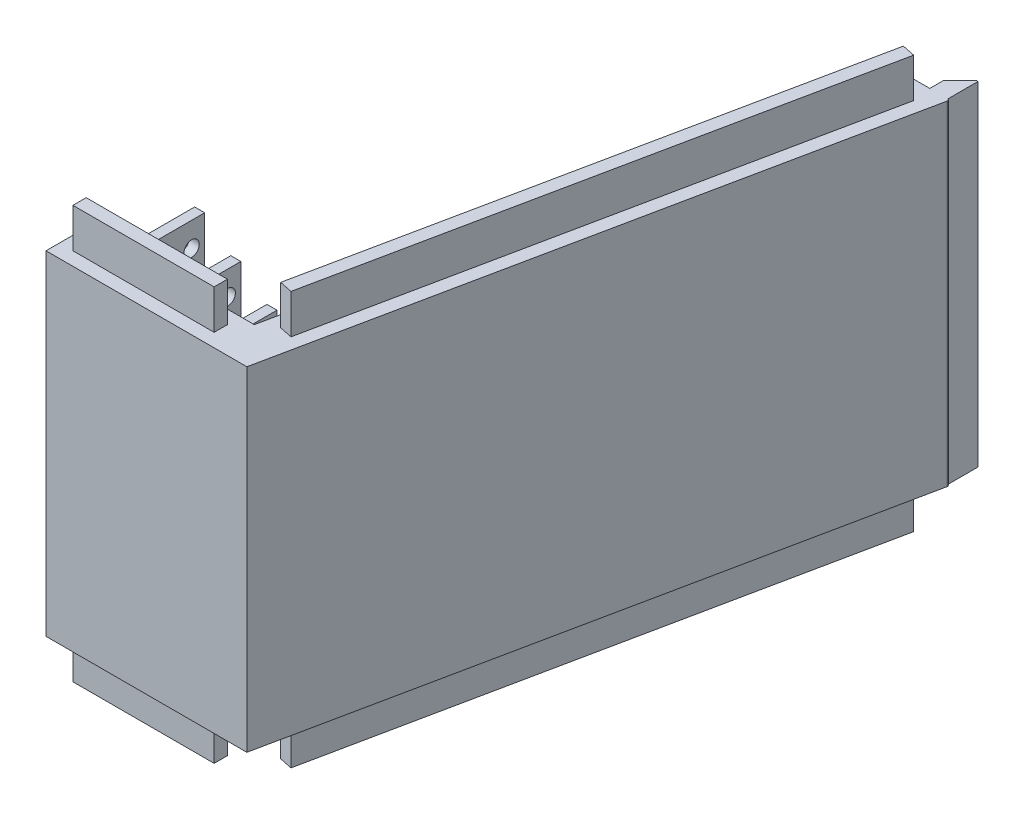
SolidWorks part; units mm, degrees
ref_plane "Front Plane" through (0, 0, 0) normal (1, 0, 0) x (0, 1, 0)
ref_plane "Top Plane" through (0, 0, 0) normal (0, 0, 1) x (0, 1, 0)
ref_plane "Right Plane" through (0, 0, 0) normal (0, 1, 0) x (-1, 0, 0)
sketch "Sketch1" plane through (0, 0, 0) normal (0, 1, 0) x (-1, 0, 0)
  line L0 (-10.3119, 2.5706) -> (19.6881, 147.5706)
  line L1 (-10.3119, -4.9294) -> (-5.3119, -4.9294)
  line L2 (-10.3119, -4.9294) -> (-10.3119, 2.5706)
  line L3 (-10.3119, 2.5706) -> (-5.3119, 2.5706)
  line L4 (-5.3119, -4.9294) -> (-5.3119, 2.5706)
  line L13 (-10.3119, 2.5706) -> (19.6881, 147.5706)
  line L14 (-10.3119, 2.5706) -> (-0.5193, 0.5446)
  line L15 (-10.3119, 2.5706) -> (69.6881, 2.5706) construction
  line L16 (-10.3119, 2.5706) -> (-10.3119, 137.5706) construction
  line L17 (-10.3119, 137.5706) -> (69.6881, 137.5706) construction
  line L18 (69.6881, 2.5706) -> (69.6881, 137.5706) construction
  line L19 (69.6881, 137.5706) -> (19.6881, 137.5706)
  line L20 (69.6881, 137.5706) -> (69.6881, 147.5706)
  line L21 (69.6881, 147.5706) -> (19.6881, 147.5706)
  line L22 (19.6881, 137.5706) -> (19.6881, 147.5706)
  line L23 (19.6881, 147.5706) -> (29.4807, 145.5446)
  line L24 (-0.5193, 0.5446) -> (29.4807, 145.5446)
  line L25 (-5.3119, 2.5706) -> (-0.1001, 2.5706)
  line L27 (-10.3119, 2.5706) -> (-9.8119, 2.5706)
  line L28 (-10.3119, 2.5706) -> (-10.3119, -4.9294)
  line L29 (-10.3119, -4.9294) -> (-9.8119, -4.9294)
  line L30 (-9.8119, 2.5706) -> (-9.8119, -4.9294)
  dimension "D1" = 7.5
  dimension "D2" = 5
  dimension "D3" = 135
  dimension "D4" = 80
  dimension "D7" = 10
  dimension "D6" = 50
extrude "Boss-Extrude1" add sketch "Sketch1" along normal blind 83.125 contours L24 L19 L20 L21 L23 | L19 L24 L23 L22 | L3 L25 L24 L19 L22 L0 | L14 L2 L1 L4 | L3 L14 L4
sketch "Sketch2" plane through (0, 83.125, 0) normal (0, 1, 0) x (-1, 0, 0)
  line L0 (27.8309, 137.5706) -> (-0.1001, 2.5706)
  line L1 (27.8309, 137.5706) -> (69.6881, 137.5706)
  line L2 (27.8309, 137.5706) -> (27.8309, 147.5706)
  line L3 (27.8309, 147.5706) -> (69.6881, 147.5706)
  line L4 (69.6881, 137.5706) -> (69.6881, 147.5706)
  line L5 (27.8309, 137.5706) -> (18.0383, 139.5967)
  line L6 (-0.1001, 2.5706) -> (-9.8927, 4.5967)
  line L7 (18.0383, 139.5967) -> (-9.8927, 4.5967)
  line L8 (-5.3119, 2.5706) -> (-0.1001, 2.5706) construction
  line L9 (23.8717, 134.9688) -> (-2.7019, 6.5299)
  line L10 (-2.7019, 6.5299) -> (-5.9335, 7.1985)
  line L11 (20.6401, 135.6374) -> (-5.9335, 7.1985)
  line L12 (23.8717, 134.9688) -> (20.6401, 135.6374)
  line L13 (31.1809, 140.9206) -> (31.1809, 144.2206)
  line L14 (31.1809, 144.2206) -> (66.3381, 144.2206)
  line L15 (66.3381, 140.9206) -> (66.3381, 144.2206)
  line L16 (31.1809, 140.9206) -> (66.3381, 140.9206)
  line L17 (69.6881, 137.5706) -> (69.6881, 147.5706) construction
  line L18 (20.6401, 135.6374) -> (23.109, 147.5706)
  line L20 (23.8717, 134.9688) -> (26.4789, 147.5706)
  line L21 (26.4789, 147.5706) -> (23.109, 147.5706)
  line L22 (31.1809, 144.2206) -> (22.4159, 144.2206)
  line L23 (22.4159, 144.2206) -> (21.7332, 140.9206)
  line L24 (21.7332, 140.9206) -> (31.1809, 140.9206)
  line L25 (-10.3119, 2.5706) -> (19.6881, 147.5706) construction
  dimension "D2" = 145
  dimension "D1" = 3.35
extrude "Boss-Extrude2" add sketch "Sketch2" along normal blind 9.8 contours L9 L12 L11 L10 | L13 L16 L15 L14
ref_plane "Plane1" through (0, 41.5625, 0) normal (0, 1, 0) x (1, 0, 0)
mirror "Mirror1" about plane through (0, 41.5625, 0) normal (0, 1, 0) of "Boss-Extrude2"
sketch "Sketch3" plane through (0, 83.125, 0) normal (0, 1, 0) x (-1, 0, 0)
  line L1 (4.0378, 22.5706) -> (69.6881, 22.5706) construction
  line L2 (4.0378, 22.5706) -> (4.0378, 137.5706) construction
  line L3 (4.0378, 137.5706) -> (69.6881, 137.5706) construction
  line L4 (69.6881, 22.5706) -> (69.6881, 137.5706) construction
  line L5 (69.6881, 22.5706) -> (4.0378, 22.5706)
  line L6 (69.6881, 22.5706) -> (69.6881, 27.5706)
  line L7 (69.6881, 27.5706) -> (4.0378, 27.5706)
  line L8 (4.0378, 22.5706) -> (4.0378, 27.5706)
  line L9 (-0.1001, 2.5706) -> (27.8309, 137.5706) construction
  line L10 (57.1881, 22.5706) -> (59.6881, 22.5706)
  line L11 (57.1881, 22.5706) -> (57.1881, 12.5706)
  line L12 (57.1881, 12.5706) -> (59.6881, 12.5706)
  line L13 (59.6881, 22.5706) -> (59.6881, 12.5706)
  line L14 (34.6881, 22.5706) -> (37.1881, 22.5706)
  line L15 (34.6881, 22.5706) -> (34.6881, 12.5706)
  line L16 (34.6881, 12.5706) -> (37.1881, 12.5706)
  line L17 (37.1881, 22.5706) -> (37.1881, 12.5706)
  line L18 (12.1881, 22.5706) -> (14.6881, 22.5706)
  line L19 (12.1881, 22.5706) -> (12.1881, 12.5706)
  line L20 (12.1881, 12.5706) -> (14.6881, 12.5706)
  line L21 (14.6881, 22.5706) -> (14.6881, 12.5706)
  line L22 (57.1881, 12.5706) -> (37.1881, 12.5706)
  line L23 (57.1881, 12.5706) -> (57.1881, 22.5706)
  line L24 (57.1881, 22.5706) -> (37.1881, 22.5706)
  line L25 (37.1881, 12.5706) -> (37.1881, 22.5706)
  line L26 (57.1881, 12.5706) -> (37.1881, 22.5706) construction
  line L27 (57.1881, 22.5706) -> (37.1881, 12.5706) construction
  line L28 (34.6881, 12.5706) -> (14.6881, 12.5706)
  line L29 (34.6881, 12.5706) -> (34.6881, 22.5706)
  line L30 (34.6881, 22.5706) -> (14.6881, 22.5706)
  line L31 (14.6881, 12.5706) -> (14.6881, 22.5706)
  line L32 (34.6881, 12.5706) -> (14.6881, 22.5706) construction
  line L33 (34.6881, 22.5706) -> (14.6881, 12.5706) construction
  line L34 (-0.1001, 2.5706) -> (4.0378, 2.5706) construction
  line L35 (-0.1001, 2.5706) -> (-0.1001, 22.5706) construction
  line L36 (-0.1001, 22.5706) -> (4.0378, 22.5706) construction
  line L37 (4.0378, 2.5706) -> (4.0378, 22.5706) construction
  line L38 (-0.1001, 2.5706) -> (4.0378, 22.5706) construction
  line L39 (-0.1001, 22.5706) -> (4.0378, 2.5706) construction
  point P20 (69.6881, 25.0706)
  point P21 (4.0378, 25.0706)
  point P24 (47.1881, 17.5706)
  point P25 (24.6881, 17.5706)
  point P29 (1.9688, 12.5706)
  line M17 (-0.1001, 2.5706) -> (27.8309, 137.5706)
  dimension "D2" = 5
  dimension "D1" = 65.6503
  dimension "D3" = 2.5
  dimension "D4" = 2.5
  dimension "D7" = 20
  dimension "D8" = 20
  dimension "D9" = 8.1503
  dimension "D11" = 20
extrude "Boss-Extrude3" [suppressed] add sketch "Sketch3" against normal blind 176 contours L6 L7 L5 M17 | L21 L5 L19 L20 | L17 L5 L15 L16 | L13 L5 L11 L12
sketch "Sketch4" [suppressed] plane through (-14.6881, 0, 0) normal (-1, 0, 0) x (0, -1, 0)
  line L1 (-83.125, 27.5706) -> (-77.625, 27.5706) construction
  line L2 (-83.125, 27.5706) -> (-83.125, 31.6956) construction
  line L3 (-83.125, 31.6956) -> (-77.625, 31.6956) construction
  line L4 (-77.625, 27.5706) -> (-77.625, 31.6956) construction
  circle A0 centre (-77.625, 31.6956) radius 1.9
  circle A1 centre (79.2, 31.6956) radius 1.9
  dimension "D3" = 3.8
  dimension "D1" = 5.5
  dimension "D2" = 4.125
  dimension "D5" = 156.825
extrude "Cut-Extrude2" [suppressed] cut sketch "Sketch4" against normal up to next
sketch "Sketch5" [suppressed] plane through (-37.1881, 0, 0) normal (-1, 0, 0) x (0, -1, 0)
  line L1 (-83.125, 27.5706) -> (-72.625, 27.5706) construction
  line L2 (-83.125, 27.5706) -> (-83.125, 31.6956) construction
  line L3 (-83.125, 31.6956) -> (-72.625, 31.6956) construction
  line L4 (-72.625, 27.5706) -> (-72.625, 31.6956) construction
  circle A0 centre (-72.625, 31.6956) radius 1.9
  circle A3 centre (84.2, 31.6956) radius 1.9
  dimension "D3" = 3.8
  dimension "D5" = 156.825
  dimension "D1" = 4.125
  dimension "D2" = 10.5
extrude "Cut-Extrude3" [suppressed] cut sketch "Sketch5" against normal up to next
sketch "Sketch6" [suppressed] plane through (-59.6881, 0, 0) normal (-1, 0, 0) x (0, -1, 0)
  line L0 (-83.125, 17.5706) -> (-83.125, 37.5706) construction
  line L1 (-83.125, 27.5706) -> (-67.625, 27.5706) construction
  line L2 (-83.125, 27.5706) -> (-83.125, 31.4206) construction
  line L3 (-83.125, 31.4206) -> (-67.625, 31.4206) construction
  line L4 (-67.625, 27.5706) -> (-67.625, 31.4206) construction
  circle A0 centre (-67.625, 31.4206) radius 1.9
  circle A1 centre (44.965, 31.4206) radius 1.9
  dimension "D3" = 3.8
  dimension "D1" = 3.85
  dimension "D2" = 15.5
extrude "Cut-Extrude4" [suppressed] cut sketch "Sketch6" against normal up to next
sketch "Sketch7" plane through (0, 83.125, 0) normal (0, 1, 0) x (-1, 0, 0)
  line L1 (27.8309, 137.5706) -> (69.6881, 137.5706) construction
  line L2 (27.8309, 137.5706) -> (27.8309, 127.5706) construction
  line L3 (27.8309, 127.5706) -> (69.6881, 127.5706) construction
  line L4 (69.6881, 137.5706) -> (69.6881, 127.5706) construction
  line L5 (69.6881, 137.5706) -> (64.6881, 137.5706) construction
  line L6 (69.6881, 137.5706) -> (69.6881, 127.5706) construction
  line L7 (69.6881, 127.5706) -> (64.6881, 127.5706) construction
  line L8 (64.6881, 137.5706) -> (64.6881, 127.5706) construction
  line L9 (64.6881, 137.5706) -> (62.1881, 137.5706)
  line L10 (64.6881, 137.5706) -> (64.6881, 127.5706)
  line L11 (64.6881, 127.5706) -> (62.1881, 127.5706)
  line L12 (62.1881, 137.5706) -> (62.1881, 127.5706)
  line L13 (62.1881, 137.5706) -> (49.6881, 137.5706) construction
  line L14 (62.1881, 137.5706) -> (62.1881, 127.5706) construction
  line L15 (62.1881, 127.5706) -> (49.6881, 127.5706) construction
  line L16 (49.6881, 137.5706) -> (49.6881, 127.5706) construction
  line L17 (49.6881, 137.5706) -> (47.1881, 137.5706)
  line L18 (49.6881, 137.5706) -> (49.6881, 127.5706)
  line L19 (49.6881, 127.5706) -> (47.1881, 127.5706)
  line L20 (47.1881, 137.5706) -> (47.1881, 127.5706)
  line L21 (47.1881, 137.5706) -> (27.8309, 137.5706) construction
  line L22 (47.1881, 137.5706) -> (47.1881, 127.5706) construction
  line L23 (47.1881, 127.5706) -> (27.8309, 127.5706) construction
  line L24 (27.8309, 137.5706) -> (27.8309, 127.5706) construction
  line L25 (47.1881, 127.5706) -> (49.6881, 127.5706)
  line L26 (47.1881, 127.5706) -> (47.1881, 121.5706)
  line L27 (47.1881, 121.5706) -> (49.6881, 121.5706)
  line L28 (49.6881, 127.5706) -> (49.6881, 121.5706)
  line L29 (32.1881, 137.5706) -> (34.6881, 137.5706)
  line L30 (32.1881, 137.5706) -> (32.1881, 127.5706)
  line L31 (32.1881, 127.5706) -> (34.6881, 127.5706)
  line L32 (34.6881, 137.5706) -> (34.6881, 127.5706)
  line L37 (62.1881, 127.5706) -> (64.6881, 127.5706)
  line L38 (62.1881, 127.5706) -> (62.1881, 115.5706)
  line L39 (62.1881, 115.5706) -> (64.6881, 115.5706)
  line L40 (64.6881, 127.5706) -> (64.6881, 115.5706)
  line L41 (49.6881, 137.5706) -> (62.1881, 137.5706)
  line L42 (49.6881, 137.5706) -> (49.6881, 132.5706)
  line L43 (49.6881, 132.5706) -> (62.1881, 132.5706)
  line L44 (62.1881, 137.5706) -> (62.1881, 132.5706)
  point P22 (47.1881, 132.5706)
  line M10 (27.8309, 137.5706) -> (69.6881, 137.5706)
  dimension "D2" = 5
  dimension "D3" = 2.5
  dimension "D4" = 2.5
  dimension "D5" = 12.5
  dimension "D8" = 12.5
  dimension "D10" = 4.3572
  dimension "D9" = 2.5
  dimension "D6" = 12
  dimension "D11" = 5
extrude "Boss-Extrude4" add sketch "Sketch7" against normal up to surface (83.125 mm away) contours L20 L19 L18 M10 | L28 L19 L26 L27 | L12 L11 L10 M10 | L40 L11 L38 L39 | L32 L30 L31 M10 | L18 L43 L12 M10 up to face at (-48.7595, 0, 142.5706)
sketch "Sketch8" plane through (-49.6881, 0, 0) normal (-1, 0, 0) x (0, -1, 0)
  line L0 (0, 134.9688) -> (0, 6.5299) construction
  line L1 (-83.125, 121.5706) -> (-72.9725, 121.5706) construction
  line L2 (-83.125, 121.5706) -> (-83.125, 124.8206) construction
  line L3 (-83.125, 124.8206) -> (-72.9725, 124.8206) construction
  line L4 (-72.9725, 121.5706) -> (-72.9725, 124.8206) construction
  line L5 (0, 121.5706) -> (-83.125, 121.5706) construction
  circle A0 centre (-72.9725, 124.8206) radius 1.9
  circle A1 centre (-10.1525, 124.8206) radius 1.9
  dimension "D3" = 3.8
  dimension "D1" = 3.25
  dimension "D2" = 10.1525
  dimension "D5" = 10.1525
  dimension "D6" = 3.25
extrude "Cut-Extrude5" cut sketch "Sketch8" against normal up to next
sketch "Sketch9" plane through (-64.6881, 0, 0) normal (-1, 0, 0) x (0, -1, 0)
  line L2 (-83.125, 115.5706) -> (-72.9725, 115.5706) construction
  line L3 (-83.125, 115.5706) -> (-83.125, 118.8206) construction
  line L4 (-83.125, 118.8206) -> (-72.9725, 118.8206) construction
  line L5 (-72.9725, 115.5706) -> (-72.9725, 118.8206) construction
  line L6 (0, 134.9688) -> (0, 6.5299) construction
  circle A1 centre (-72.9725, 118.8206) radius 1.9
  circle A2 centre (-18.9025, 118.8206) radius 1.9
  circle A3 centre (-10.1525, 118.8206) radius 1.9
  circle A4 centre (-72.9725, 124.8206) radius 1.9 construction
  circle A5 centre (-10.1525, 124.8206) radius 1.9 construction
  circle A6 centre (-64.2225, 118.8206) radius 1.9
  dimension "D3" = 3.8
  dimension "D1" = 3.25
  dimension "D2" = 10.1525
  dimension "D6" = 62.82
  dimension "D8" = 54.07
  dimension "D9" = 54.07
  dimension "D10" = 10.1525
extrude "Cut-Extrude6" cut sketch "Sketch9" against normal up to next
sketch "Sketch12" plane through (-34.6881, 0, 0) normal (-1, 0, 0) x (0, -1, 0)
  line L1 (-83.125, 127.5019) -> (-72.9725, 127.5019) construction
  line L2 (-83.125, 127.5019) -> (-83.125, 130.7519) construction
  line L3 (-83.125, 130.7519) -> (-72.9725, 130.7519) construction
  line L4 (-72.9725, 127.5019) -> (-72.9725, 130.7519) construction
  line L5 (-83.125, 134.9688) -> (-83.125, 6.5299) construction
  line L6 (0, 127.5706) -> (0, 137.5706) construction
  circle A0 centre (-72.9725, 130.7519) radius 1.9
  circle A1 centre (-10.1525, 130.7519) radius 1.9
  dimension "D3" = 3.8
  dimension "D1" = 10.1525
  dimension "D2" = 3.25
  dimension "D5" = 62.82
  dimension "D6" = 10.1525
extrude "Cut-Extrude9" cut sketch "Sketch12" against normal up to next
sketch "Sketch10" plane through (-64.6881, 0, 0) normal (-1, 0, 0) x (0, -1, 0)
  line L0 (-83.125, 137.5706) -> (0, 137.5706) construction
  line L1 (-83.125, 115.5706) -> (-58.125, 115.5706) construction
  line L2 (-83.125, 115.5706) -> (-83.125, 137.5706) construction
  line L3 (-83.125, 137.5706) -> (-58.125, 137.5706) construction
  line L4 (-58.125, 115.5706) -> (-58.125, 137.5706) construction
  line L6 (-58.125, 137.5706) -> (-25, 137.5706)
  line L7 (-58.125, 137.5706) -> (-58.125, 115.5706)
  line L8 (-58.125, 115.5706) -> (-25, 115.5706)
  line L9 (-25, 137.5706) -> (-25, 115.5706)
  line L11 (-25, 115.5706) -> (0, 115.5706) construction
  line L12 (-25, 115.5706) -> (-25, 137.5706) construction
  line L13 (-25, 137.5706) -> (0, 137.5706) construction
  line L14 (0, 115.5706) -> (0, 137.5706) construction
  line L16 (-83.125, 137.5706) -> (-79.07, 137.5706)
  line L17 (-83.125, 137.5706) -> (-83.125, 115.5706)
  line L18 (-83.125, 115.5706) -> (-79.07, 115.5706)
  line L19 (-79.07, 137.5706) -> (-79.07, 115.5706)
  line L20 (0, 137.5706) -> (-4.055, 137.5706)
  line L21 (0, 137.5706) -> (0, 115.5706)
  line L22 (0, 115.5706) -> (-4.055, 115.5706)
  line L23 (-4.055, 137.5706) -> (-4.055, 115.5706)
  circle A0 centre (-18.9025, 118.8206) radius 1.9 construction
  circle A1 centre (-10.1525, 118.8206) radius 1.9 construction
  circle A2 centre (-64.2225, 118.8206) radius 1.9 construction
  circle A3 centre (-72.9725, 118.8206) radius 1.9 construction
  dimension "D1" = 25
  dimension "D2" = 25
  dimension "D3" = 6.0975
  dimension "D4" = 6.0975
  dimension "D5" = 4.055
  dimension "D6" = 6.0975
  dimension "D7" = 6.0975
extrude "Cut-Extrude7" cut sketch "Sketch10" against normal up to surface (32.5 mm away) up to face at (-32.1881, 72.9725, 128.8519)
sketch "Sketch11" plane through (0.606, 0, 0.1254) normal (-0.9793, 0, -0.2026) x (0, -1, 0)
  line L0 (-83.125, -5.9034) -> (-83.125, 1.4411) construction
  line L1 (-83.125, 15.9262) -> (0, 15.9262)
  line L2 (-83.125, 15.9262) -> (-83.125, 140.3562)
  line L3 (-83.125, 140.3562) -> (0, 140.3562)
  line L4 (0, 15.9262) -> (0, 140.3562)
  line L8 (-68.125, 1.4411) -> (-68.125, 140.3562)
  line L12 (-15, 1.4411) -> (-15, 140.3562)
  line L13 (-83.125, 1.4411) -> (0, 1.4411) construction
  line M8 (-83.125, 2.497) -> (0, 2.497)
  dimension "D1" = 15
extrude "Cut-Extrude8" cut sketch "Sketch11" against normal blind 5 contours L1 L12 L3 L8 | L1 L12 L8 M8
chamfer "Chamfer1" distance 4 angle 45 1 edges at (5.3119, 41.5625, -4.9294)
fillet "Fillet1" radius 0.5 1 edges at (10.3119, 41.5625, 2.5706)
chamfer "Chamfer2" distance 10 angle 30 2 edges at (-13.8654, 68.125, 70.0706) (-13.8654, 15, 70.0706)
equation "\"whitekey_cutout_length\"= 101.5"
equation "\"key_mount_recess_length\"=50"
equation "\"key_mount_recess_height\"=12.5"
equation "\"key_mount_recess_depth\"=1.5"
equation "\"wall_thickness\"=10"
equation "\"guide_brace_height\"=20"
equation "\"guide_brace_thickness\"=2"
equation "\"dowel_recess_depth\"=10"
equation "\"dowel_recess_offset\"=3.25"
equation "\"dowel_insert_tolerance\"=0.1"
equation "\"base_mount_height\"=40"
equation "\"base_rear_length\"=80"
equation "\"base_front_length\"=111.5"
equation "\"screw_hole_wall_offset\"=7.25"
equation "\"screw_hole_edge_inset\"=\"dowel_recess_depth\"/2"
equation "\"screw_hole_diameter\"=3.8"
equation "\"screw_head_hole_diameter\"=6.7"
equation "\"screw_nut_hole_side_len\"=3.5"
equation "\"screw_nut_recess_offset\"=0.35"
equation "\"screw_head_and_nut_recess_depth\"=2.5"
equation "\"screw_shaft_diameter\"=3.5"
equation "\"switch_board_width\"=30"
equation "\"switch_board_thickness\"=1.6"
equation "\"switch_board_wall_offset\"=11.5"
equation "\"heatset_insert_hole_diameter\"=4.8"
equation "\"heatset_insert_hole_depth\"=3.8"
equation "\"front_rear_panel_width\"=23.75"
equation "\"front_panel_height\"=24"
equation "\"front_rear_panel_recess_depth\"=5"
equation "\"rod_diameter\"=5"
equation "\"rod_head_diameter\"=8"
equation "\"rod_length_adj\"=0.5"
equation "\"rod_insert_length\"=2.8"
equation "\"switch_black_key_mount_height\"=8"
equation "\"switch_white_key_mount_height\"=3"
equation "\"D7@Sketch1\"=\"wall_thickness\""
equation "\"D5@Sketch1\"=\"wall_thickness\""
equation "\"D2@Sketch1\"=\"wall_thickness\"/2"
equation "\"D4@Sketch1\"=\"base_rear_length\""
equation "\"D3@Sketch1\"=\"interface_panel_height\""
equation "\"D1@Sketch1\"=\"wall_thickness\"*0.75"
equation "\"D1@Boss-Extrude1\"=\"front_rear_panel_width\"*3.5"
equation "\"D1@Sketch2\"=\"dowel_recess_offset\"+\"dowel_insert_tolerance\""
equation "\"D1@Boss-Extrude2\"=\"dowel_recess_depth\"-\"dowel_insert_tolerance\"*2"
equation "\"D2@Sketch3\"=\"wall_thickness\"/2"
equation "\"D3@Sketch3\"=\"wall_thickness\"/4"
equation "\"D4@Sketch3\"=\"wall_thickness\"/4"
equation "\"D5@Sketch3\"=\"wall_thickness\"/4"
equation "\"D6@Sketch3\"=\"wall_thickness\""
equation "\"D7@Sketch3\"=\"wall_thickness\"*2"
equation "\"D8@Sketch3\"=\"wall_thickness\"*2"
equation "\"D10@Sketch3\"=\"wall_thickness\""
equation "\"D3@Sketch4\"=\"screw_hole_diameter\""
equation "\"D3@Sketch5\"=\"screw_hole_diameter\""
equation "\"D3@Sketch6\"=\"screw_hole_diameter\""
equation "\"D1@Sketch7\"=\"wall_thickness\""
equation "\"D2@Sketch7\"=\"wall_thickness\"*0.5"
equation "\"D3@Sketch7\"=\"wall_thickness\"/4"
equation "\"D4@Sketch7\"=\"wall_thickness\"/4"
equation "\"D5@Sketch7\"=\"wall_thickness\"*1.25"
equation "\"D7@Sketch7\"=\"wall_thickness\"*0.6"
equation "\"D3@Sketch8\"=\"screw_hole_diameter\""
equation "\"D3@Sketch9\"=\"screw_hole_diameter\""
equation "\"D1@Sketch11\"=\"dowel_recess_depth\"*1.5"
equation "\"D2@Sketch11\"=\"dowel_recess_depth\"*1.5"
equation "\"D1@Cut-Extrude8\"=\"wall_thickness\"/2"
equation "\"whitekey_spacing\"=1.25"
equation "\"side_panel_depth\"=35"
equation "\"D8@Sketch1\"=\"whitekey_spacing\"*0.4"
equation "\"interface_panel_height\"=135"
equation "\"interface_panel_roof_length\"=50"
equation "\"D6@Sketch1\"=\"interface_panel_roof_length\""
equation "\"D8@Sketch7\"=\"wall_thickness\"*1.25"
equation "\"D9@Sketch7\"=\"wall_thickness\"/4"
equation "\"D6@Sketch7\"=\"D7@Sketch7\"*2"
equation "\"D4@Sketch10\"=\"D3@Sketch10\""
equation "\"D7@Sketch10\"=\"D3@Sketch10\""
equation "\"D3@Sketch12\"=\"screw_hole_diameter\""
equation "\"D11@Sketch7\"=\"wall_thickness\"/2"
